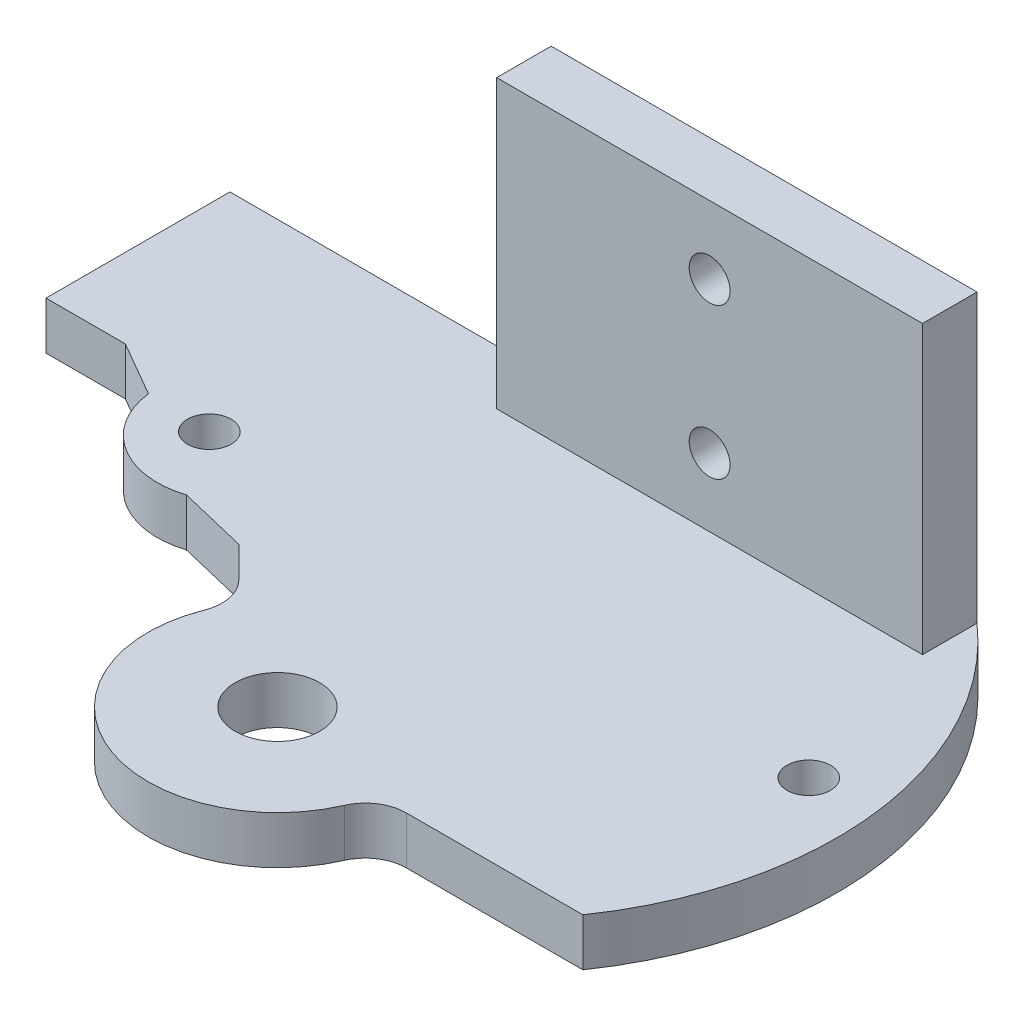
SolidWorks part; units mm, degrees
ref_plane "Alzado" through (0, 0, 0) normal (0, 0, 1) x (1, 0, 0)
ref_plane "Planta" through (0, 0, 0) normal (0, 1, 0) x (1, 0, 0)
ref_plane "Vista lateral" through (0, 0, 0) normal (1, 0, 0) x (0, 0, -1)
sketch "Croquis1" plane through (0, 0, 0) normal (0, 1, 0) x (1, 0, 0)
  line L0 (-35, 32.5) -> (35, -32.5) construction
  line L1 (-35, 32.5) -> (35, 32.5)
  line L2 (-35, 32.5) -> (-35, -32.5)
  line L3 (-35, -32.5) -> (35, -32.5)
  line L4 (35, 32.5) -> (35, -32.5)
  dimension "D1" = 70
  dimension "D2" = 65
extrude "Extruir1" add sketch "Croquis1" along normal blind 3.5
sketch "Croquis2" plane through (0, 3.5, 0) normal (0, 1, 0) x (1, 0, 0)
  line L0 (0, 32.5) -> (0, -32.5) construction
  line L1 (35, 32.5) -> (-35, 32.5) construction
  line L2 (-35, -32.5) -> (35, -32.5) construction
  circle A0 centre (0, -17.5) radius 3.1
  dimension "D1" = 6.2
  dimension "D2" = 15
extrude "Extruir2" cut sketch "Croquis2" against normal blind 5
sketch "Croquis3" plane through (0, 3.5, 0) normal (0, 1, 0) x (1, 0, 0)
  line L0 (0, -32.5) -> (0, 32.5) construction
  line L1 (-35, -32.5) -> (35, -32.5) construction
  line L2 (35, 32.5) -> (-35, 32.5) construction
  line L3 (-32.9868, -32.5) -> (-32.9868, 32.5) construction
  line L4 (-32.9868, 1.5) -> (-12.9615, 1.5)
  line L5 (18.8496, -32.5) -> (18.8496, 32.5) construction
  line L6 (-32.9868, 3.5) -> (18.8496, 3.5) construction
  line L7 (-32.9868, 2) -> (0, 2) construction
  line L8 (-32.9868, 11.5) -> (18.8496, 11.5) construction
  line L9 (0, -17.5) -> (-14.8492, -2.6508) construction
  line L10 (0, -17.5) -> (14.8492, -2.6508) construction
  line L11 (0, 2) -> (18.8496, 2) construction
  line L12 (-32.9868, 2) -> (18.8496, 2) construction
  line L13 (-32.9868, 12) -> (18.8496, 12)
  line L14 (-5.3033, -12.1967) -> (-16.2635, -1.2365) construction
  line L15 (12.9615, 1.5) -> (18.8496, 1.5)
  line L16 (-32.9868, 1.5) -> (18.8496, 1.5) construction
  line L17 (7.9844, -18) -> (22.9946, -18)
  line L18 (-5.9993, -12.2078) -> (-16.6132, -1.5939)
  line L19 (0, -17.5) -> (23, -17.5) construction
  line L20 (7.5, -17.5) -> (23, -17.5) construction
  line L21 (-5.6569, -12.5503) -> (-16.617, -1.5901) construction
  line L22 (7.5, -18) -> (23, -18) construction
  line L23 (-32.9868, 12) -> (-32.9868, 1.5)
  line L24 (18.8496, 12) -> (18.8496, 1.5)
  line L25 (-34.4868, 13.5) -> (20.3496, 13.5)
  line L26 (20.3496, 13.5) -> (20.3496, 0)
  line L27 (17.1464, 0) -> (20.3496, 0)
  line L28 (9.2871, -19.5) -> (24.4182, -19.5)
  line L29 (-7.9812, -12.3473) -> (-18.6805, -1.6479)
  line L30 (-34.4868, 0) -> (-17.1464, 0)
  line L31 (-34.4868, 13.5) -> (-34.4868, 0)
  circle A0 centre (0, -17.5) radius 21 construction
  circle A1 centre (0, -17.5) radius 7.5 construction
  arc A2 (-12.9615, 1.5) -> (-16.6132, -1.5939) centre (0, -17.5) ccw
  circle A3 centre (0, -17.5) radius 23 construction
  arc A4 (-5.9993, -12.2078) -> (7.9844, -18) centre (0, -17.5) ccw
  arc A5 (22.9946, -18) -> (12.9615, 1.5) centre (0, -17.5) ccw
  arc A6 (24.4182, -19.5) -> (17.1464, 0) centre (0, -17.5) ccw
  arc A7 (-7.9812, -12.3473) -> (9.2871, -19.5) centre (0, -17.5) ccw
  arc A8 (-17.1464, 0) -> (-18.6805, -1.6479) centre (0, -17.5) ccw
  dimension "D3" = 42
  dimension "D8" = 15
  dimension "D9" = 46
  dimension "D14" = 0.5
  dimension "D2" = 51.8364
  dimension "D6" = 90
  dimension "D7" = 45
  dimension "D1" = 32.9868
  dimension "D4" = 1.5
  dimension "D5" = 9.5
  dimension "D10" = 2
  dimension "D11" = 0.5
  dimension "D12" = 0.5
  dimension "D13" = 0.5
  dimension "D15" = 1.5
extrude "Extruir3" add sketch "Croquis3" along normal blind 10
sketch "Croquis4" plane through (0, 3.5, 0) normal (0, 1, 0) x (1, 0, 0)
  line L0 (-34.4868, 0) -> (-17.1464, 0) construction
  line L1 (-34.4868, 13.5) -> (-34.4868, 0) construction
  line L2 (20.3496, 13.5) -> (-34.4868, 13.5) construction
  line L3 (20.3496, 0) -> (20.3496, 13.5) construction
  line L4 (17.1464, 0) -> (20.3496, 0) construction
  line L5 (9.2871, -19.5) -> (24.4182, -19.5) construction
  line L6 (-18.6805, -1.6479) -> (-7.9812, -12.3473) construction
  line L7 (-34.4868, 0) -> (-17.1464, 0)
  line L8 (-34.4868, 13.5) -> (-34.4868, 0)
  line L9 (20.3496, 13.5) -> (-34.4868, 13.5)
  line L10 (20.3496, 0) -> (20.3496, 13.5)
  line L11 (17.1464, 0) -> (20.3496, 0)
  line L12 (9.2871, -19.5) -> (24.4182, -19.5)
  line L13 (-18.6805, -1.6479) -> (-7.9812, -12.3473)
  arc A0 (-17.1464, 0) -> (-18.6805, -1.6479) centre (0, -17.5) ccw construction
  arc A1 (24.4182, -19.5) -> (17.1464, 0) centre (0, -17.5) ccw construction
  arc A2 (-7.9812, -12.3473) -> (9.2871, -19.5) centre (0, -17.5) ccw construction
  arc A3 (-17.1464, 0) -> (-18.6805, -1.6479) centre (0, -17.5) ccw
  arc A4 (24.4182, -19.5) -> (17.1464, 0) centre (0, -17.5) ccw
  arc A5 (-7.9812, -12.3473) -> (9.2871, -19.5) centre (0, -17.5) ccw
extrude "Extruir4" cut sketch "Croquis4" against normal blind 10 flip side to cut
fillet "Redondeo1" radius 3 4 edges at (9.2871, 6.75, 19.5) (-7.9812, 6.75, 12.3473) (7.9844, 8.5, 18) (-5.9993, 8.5, 12.2078)
sketch "Croquis5" plane through (0, 0, 0) normal (0, -1, 0) x (1, 0, 0)
  line L0 (-18.6805, 1.6479) -> (-9.5151, 10.8133) construction
  line L1 (-34.4868, 0) -> (-17.1464, 0) construction
  line L2 (-18.6805, 1.6479) -> (-14.4379, 5.8906)
  line L3 (-24.4498, 0) -> (-17.1464, 0)
  line L4 (20.3496, 0) -> (20.3496, -13.5) construction
  line L5 (17.1464, 0) -> (20.3496, 0) construction
  line L6 (20.3496, 0) -> (20.3496, -13.5)
  line L7 (17.1464, 0) -> (20.3496, 0)
  arc A0 (-14.4379, 5.8906) -> (-24.4498, 0) centre (-18.6805, 1.6479) ccw
  arc A1 (-18.6805, 1.6479) -> (-17.1464, 0) centre (0, 17.5) ccw construction
  arc A2 (-18.6805, 1.6479) -> (-17.1464, 0) centre (0, 17.5) ccw
  arc A3 (24.4182, 19.5) -> (20.3496, -13.5) centre (3.8531, 5.2847) cw
  arc A4 (17.1464, 0) -> (24.4182, 19.5) centre (0, 17.5) ccw construction
  arc A5 (17.1464, 0) -> (24.4182, 19.5) centre (0, 17.5) ccw
  dimension "D1" = 12
  dimension "D2" = 25
extrude "Extruir5" add sketch "Croquis5" against normal up to surface (13.5 mm away) up to face at (-1.8278, 13.5, 5.5887)
chamfer "Chaflán1" distance 5 angle 45 2 edges at (-14.4379, 6.75, 5.8906) (-24.4498, 6.75, 0) first distance on face at (-20.5835, 6.75, 4.8823) first distance on face at (-29.4683, 6.75, 0)
sketch "Croquis6" plane through (0, 13.5, 0) normal (0, 1, 0) x (1, 0, 0)
  line L7 (-34.4868, 13.5) -> (-34.4868, 0)
  line L8 (-34.4868, 0) -> (-28.6614, 0)
  line L9 (-28.6614, 0) -> (-24.6424, -2.3231)
  line L10 (-16.83, -7.3554) -> (-11.7523, -8.5761)
  line L11 (-11.7523, -8.5761) -> (-9.5151, -10.8133)
  line L12 (11.4564, -19.5) -> (24.4182, -19.5)
  line L13 (20.3496, 13.5) -> (-34.4868, 13.5)
  line L14 (-34.4868, 13.5) -> (-34.4868, 0)
  line L15 (-34.4868, 0) -> (-28.6614, 0)
  line L16 (-28.6614, 0) -> (-24.6424, -2.3231)
  line L17 (-16.83, -7.3554) -> (-11.7523, -8.5761)
  line L18 (-11.7523, -8.5761) -> (-9.5151, -10.8133)
  line L19 (11.4564, -19.5) -> (24.4182, -19.5)
  line L20 (20.3496, 13.5) -> (-34.4868, 13.5)
  arc A5 (-24.6424, -2.3231) -> (-16.83, -7.3554) centre (-18.6805, -1.6479) ccw
  arc A6 (-8.8437, -14.0303) -> (-9.5151, -10.8133) centre (-11.6365, -12.9346) ccw
  arc A7 (-8.8437, -14.0303) -> (8.7069, -21.3) centre (0, -17.5) ccw
  arc A8 (11.4564, -19.5) -> (8.7069, -21.3) centre (11.4564, -22.5) ccw
  arc A9 (24.4182, -19.5) -> (20.3496, 13.5) centre (3.8531, -5.2847) ccw
  arc A10 (-24.6424, -2.3231) -> (-16.83, -7.3554) centre (-18.6805, -1.6479) ccw
  arc A11 (-8.8437, -14.0303) -> (-9.5151, -10.8133) centre (-11.6365, -12.9346) ccw
  arc A12 (-8.8437, -14.0303) -> (8.7069, -21.3) centre (0, -17.5) ccw
  arc A13 (11.4564, -19.5) -> (8.7069, -21.3) centre (11.4564, -22.5) ccw
  arc A14 (24.4182, -19.5) -> (20.3496, 13.5) centre (3.8531, -5.2847) ccw
  dimension "D1" = 0
extrude "Extruir6" add sketch "Croquis6" along normal blind 3.5 separate body
sketch "Croquis7" plane through (0, 17, 0) normal (0, 1, 0) x (1, 0, 0)
  line L0 (20.3496, 13.5) -> (-34.4868, 13.5) construction
  circle A0 centre (-20, -2.5) radius 1.6
  circle A1 centre (24, -2.5) radius 1.6
  dimension "D1" = 3.2
  dimension "D2" = 16
  dimension "D3" = 20
  dimension "D4" = 24
extrude "Extruir7" cut sketch "Croquis7" against normal through all
sketch "Croquis8" plane through (0, 17, 0) normal (0, 1, 0) x (1, 0, 0)
  circle A0 centre (0, -17.5) radius 3.1 construction
  circle A1 centre (0, -17.5) radius 3.1
extrude "Extruir8" cut sketch "Croquis8" against normal blind 5
sketch "Croquis9" plane through (0, 13.5, 0) normal (0, 1, 0) x (1, 0, 0)
  line L0 (18.8496, 1.5) -> (18.8496, 12) construction
  line L1 (18.8496, 1.5) -> (18.8496, 12)
  line L2 (19.5496, 1.5) -> (19.5496, 12)
  line L3 (18.8496, 12) -> (19.5496, 12)
  line L4 (18.8496, 1.5) -> (19.5496, 1.5)
  dimension "D1" = 0.7
extrude "Extruir9" cut sketch "Croquis9" against normal up to surface (10 mm away) up to face at (-1.6185, 3.5, 4.8365)
sketch "Croquis10" plane through (19.5496, 0, 0) normal (-1, 0, 0) x (0, 0, 1)
  line L0 (-5.875, 13.5) -> (-5.875, 3.5) construction
  line L3 (-1.5, 13.5) -> (-12, 13.5) construction
  line L4 (-12, 3.5) -> (-12, 13.5) construction
  line L5 (-5.875, 13.5) -> (-12, 3.5) construction
  line L6 (-12, 3.5) -> (-1.5, 3.5) construction
  line L7 (-8.9375, 8.5) -> (-12, 13.5) construction
  line L8 (19.5, 13.5) -> (-13.5, 13.5) construction
  line L10 (-7.4062, 11) -> (-10.4687, 11)
  line L11 (-7.4062, 11) -> (-7.4062, 6)
  line L12 (-7.4062, 6) -> (-10.4687, 6)
  line L13 (-10.4687, 11) -> (-10.4687, 6)
  dimension "D1" = 6.125
  dimension "D2" = 5
  dimension "D3" = 3.0625
extrude "Extruir10" cut sketch "Croquis10" against normal blind 10 and the other way through all
delete or keep bodies "Sólido-Eliminar1" type delete bodies bodies 111
sketch "Croquis11" plane through (0, 0, -13.5) normal (0, 0, -1) x (-1, 0, 0)
  line L0 (34.4868, 17) -> (34.4868, 38.056)
  line L2 (-20.3496, 38.056) -> (-20.3496, 17)
  line L3 (-20.3496, 17) -> (34.4868, 17)
  line L4 (34.4868, 38.056) -> (-20.3496, 38.056)
  dimension "D2" = 21.056
extrude "Saliente-Extruir1" add sketch "Croquis11" against normal blind 4
sketch "Croquis15" plane through (0, 0, -9.5) normal (0, 0, 1) x (1, 0, 0)
  line L1 (-34.4868, 38.056) -> (-10.9056, 38.056)
  line L2 (-34.4868, 38.056) -> (-34.4868, 17)
  line L3 (-34.4868, 17) -> (-10.9056, 17)
  line L4 (-10.9056, 38.056) -> (-10.9056, 17)
extrude "Cortar-Extruir3" cut sketch "Croquis15" against normal blind 10
sketch "Croquis16" plane through (0, 0, -9.5) normal (0, 0, 1) x (1, 0, 0)
  line L0 (4.722, 17) -> (4.722, 38.056) construction
  line L1 (20.3496, 17) -> (-10.9056, 17) construction
  line L2 (-10.9056, 38.056) -> (20.3496, 38.056) construction
  circle A0 centre (4.722, 33.056) radius 1.5
  circle A1 centre (4.722, 22) radius 1.5
  dimension "D1" = 3
  dimension "D2" = 3
  dimension "D3" = 5
  dimension "D4" = 5
extrude "Cortar-Extruir4" cut sketch "Croquis16" against normal blind 10
ref_plane "Plano1" through (0, 0, -23.5) normal (0, 0, -1) x (-1, 0, 0)
move or copy body "Sólido-Mover/Copiar1" [suppressed] bodies to move or copy 119
